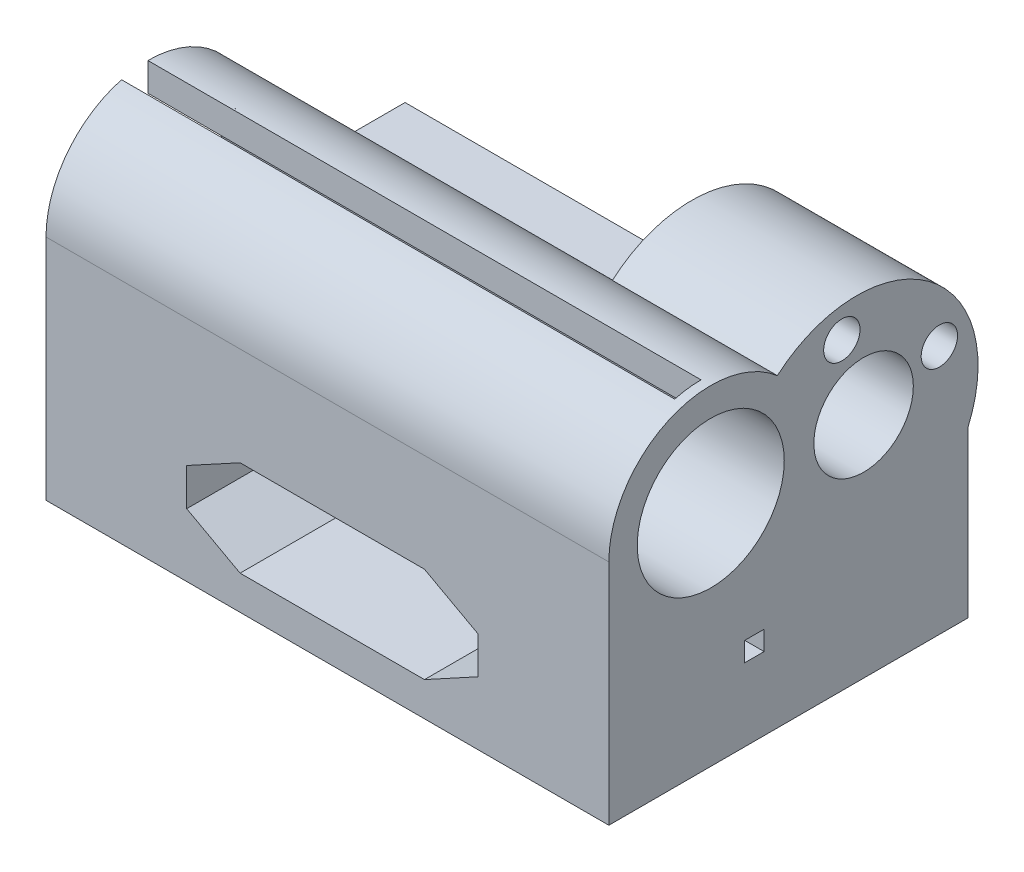
SolidWorks part; units mm, degrees
ref_plane "Front Plane" through (0, 0, 0) normal (0, 0, 1) x (1, 0, 0)
ref_plane "Top Plane" through (0, 0, 0) normal (0, 1, 0) x (1, 0, 0)
ref_plane "Right Plane" through (0, 0, 0) normal (1, 0, 0) x (0, 0, -1)
sketch "Sketch2" plane through (0, 0, 0) normal (0, 1, 0) x (1, 0, 0)
  line L1 (-29, -18.5) -> (29, -18.5)
  line L2 (-29, -18.5) -> (-29, 18.5)
  line L3 (-29, 18.5) -> (29, 18.5)
  line L4 (29, -18.5) -> (29, 18.5)
  line L5 (-29, -18.5) -> (29, 18.5) construction
  line L6 (-29, 18.5) -> (29, -18.5) construction
  point P0 (0, 0)
  dimension "D1" = 58
  dimension "D2" = 37
extrude "Boss-Extrude1" add sketch "Sketch2" along normal blind 17
sketch "Sketch3" plane through (29, 0, 0) normal (1, 0, 0) x (0, 0, -1)
  line L0 (-18.5, 0) -> (18.5, 0) construction
  line L1 (-18.5, 23.5) -> (-18.5, 17)
  line L2 (-18.5, 17) -> (-18.5, 0) construction
  line L5 (2.5, 23.5) -> (2.5, 17)
  line L6 (-18.5, 17) -> (18.5, 17) construction
  line L7 (-18.5, 17) -> (2.5, 17)
  arc A0 (2.5, 23.5) -> (-18.5, 23.5) centre (-8, 23.5) ccw
  dimension "D2" = 21
  dimension "D4" = 23.5
  dimension "D5" = 10.5
extrude "Boss-Extrude2" add sketch "Sketch3" against normal up to surface (58 mm away) up to face at (-29, 8.5, 0)
sketch "Sketch4" plane through (29, 0, 0) normal (1, 0, 0) x (0, 0, -1)
  line L1 (-18.5, 0) -> (18.5, 0) construction
  circle A0 centre (7.0436, 22) radius 12.5
  dimension "D1" = 25
  dimension "D2" = 22
extrude "Boss-Extrude3" add sketch "Sketch4" against normal blind 17
sketch "Sketch5" plane through (0, 0, -18.5) normal (0, 0, -1) x (-1, 0, 0)
  line L0 (-15.5, 6.5) -> (-15.5, 10.35)
  line L1 (-15.5, 10.35) -> (-10, 13.35)
  line L2 (-10, 13.35) -> (9, 13.35)
  line L3 (9, 13.35) -> (14.5, 10.357)
  line L4 (14.5, 10.357) -> (14.5, 6.5)
  line L5 (14.5, 6.5) -> (9, 3.5)
  line L6 (9, 3.5) -> (-10, 3.5)
  line L7 (-10, 3.5) -> (-15.5, 6.5)
  line L8 (-29, 0) -> (29, 0) construction
  line L9 (-29, 17) -> (-29, 0) construction
  line L10 (-23, 5.2045) -> (-23, 14.6536) construction
  line L11 (22, 4.2644) -> (22, 14.6536) construction
  line L12 (-23, 14.6536) -> (22, 14.6536) construction
  line L13 (-0.5, 14.6536) -> (-0.5, 7.909) construction
  line L14 (-29, 8.5) -> (29, 8.5) construction
  line L15 (29, 17) -> (29, 0) construction
  dimension "D1" = 3.85
  dimension "D2" = 3.857
  dimension "D3" = 3
  dimension "D4" = 3
  dimension "D5" = 5.5
  dimension "D6" = 5.5
  dimension "D8" = 5.5
  dimension "D9" = 19
  dimension "D10" = 3.5
  dimension "D11" = 15
  dimension "D12" = 6
  dimension "D13" = 45
extrude "Cut-Extrude1" cut sketch "Sketch5" against normal through all
sketch "Sketch6" plane through (0, 0, -18.5) normal (0, 0, -1) x (-1, 0, 0)
  line L0 (-29, 0) -> (29, 0) construction
  line L1 (-29, 17) -> (-29, 0) construction
  circle A0 centre (-23, 8.5) radius 4.076
  circle A1 centre (22, 8.5) radius 4.076
  dimension "D5" = 8.152
  dimension "D6" = 8.152
  dimension "D1" = 8.5
  dimension "D2" = 8.5
  dimension "D3" = 6
  dimension "D4" = 45
extrude "Cut-Extrude2" cut sketch "Sketch6" against normal blind 23
sketch "Sketch7" plane through (29, 0, 0) normal (1, 0, 0) x (0, 0, -1)
  line L0 (-18.5, 23.5) -> (-18.5, 0) construction
  line L1 (-18.5, 0) -> (18.5, 0) construction
  circle A0 centre (-8, 23.5) radius 7.575
  circle A1 centre (7.7501, 23.5) radius 5.125
  dimension "D1" = 10.25
  dimension "D2" = 15.15
  dimension "D3" = 26.2501
  dimension "D4" = 23.5
extrude "Cut-Extrude3" cut sketch "Sketch7" against normal through all
sketch "Sketch8" plane through (29, 0, 0) normal (1, 0, 0) x (0, 0, -1)
  line L0 (7.7501, 23.5) -> (5.5097, 31.31) construction
  line L3 (7.7501, 23.5) -> (15.5601, 25.7405) construction
  line L4 (5.5097, 31.31) -> (6.0267, 29.5077) construction
  line L7 (15.5601, 25.7405) -> (13.7578, 25.2235) construction
  circle A1 centre (5.5097, 31.31) radius 1.875
  circle A2 centre (15.5601, 25.7405) radius 1.875
  dimension "D1" = 3.75
  dimension "D2" = 6.25
  dimension "D3" = 3.75
  dimension "D7" = 6.25
extrude "Cut-Extrude4" cut sketch "Sketch8" against normal through all
sketch "Sketch12" plane through (-29, 0, 0) normal (-1, 0, 0) x (0, 0, 1)
  line L0 (-18.5, 17) -> (-18.5, 0) construction
  line L1 (4.5, 7.5) -> (2.5, 7.5)
  line L2 (4.5, 7.5) -> (4.5, 9.5)
  line L3 (4.5, 9.5) -> (2.5, 9.5)
  line L4 (2.5, 7.5) -> (2.5, 9.5)
  line L5 (-18.5, 0) -> (18.5, 0) construction
  dimension "D1" = 23
  dimension "D2" = 2
  dimension "D3" = 2
  dimension "D4" = 7.5
extrude "Cut-Extrude6" cut sketch "Sketch12" against normal blind 8
mirror "Mirror1" about plane through (0, 0, 0) normal (1, 0, 0) of "Cut-Extrude6"
sketch "Sketch13" plane through (-29, 0, 0) normal (-1, 0, 0) x (0, 0, 1)
  line L0 (8, 23.5) -> (10.7176, 33.6422) construction
  line L1 (8, 23.5) -> (-2.5, 23.5) construction
  line L2 (8, 23.5) -> (8, 34) construction
  line L3 (9.9606, 30.8169) -> (10.7176, 33.6422)
  line L4 (8, 34) -> (8, 31.075)
  arc A0 (9.9606, 30.8169) -> (8, 31.075) centre (8, 23.5) ccw
  arc A1 (-2.5, 23.5) -> (8, 34) centre (8, 23.5) ccw
  arc A2 (18.5, 23.5) -> (-2.5, 23.5) centre (8, 23.5) ccw construction
  arc A3 (1.1397, 31.449) -> (-2.5, 23.5) centre (8, 23.5) ccw construction
  circle A4 centre (8, 23.5) radius 7.575 construction
  circle M5 centre (8, 23.5) radius 7.575
  arc M8 (18.5, 23.5) -> (-2.5, 23.5) centre (8, 23.5) ccw
  dimension "D1" = 15
  dimension "D2" = 90
extrude "Cut-Extrude7" cut sketch "Sketch13" against normal blind 57 contours L4 L3 M8 M5 region at (-29, 32.5126, 9.1865)
sketch "Sketch14" plane through (0, 0, 0) normal (0, -1, 0) x (1, 0, 0)
  line L0 (0.5, -11.5) -> (29, -11.5) construction
  line L1 (29, 18.5) -> (29, -18.5) construction
  line L2 (0.5, -11.5) -> (0.5, -18.5) construction
  line L3 (29, -18.5) -> (-29, -18.5) construction
  circle A0 centre (0.5, -11.5) radius 1.5
  dimension "D1" = 3
  dimension "D2" = 7
  dimension "D3" = 28.5
extrude "Cut-Extrude8" cut sketch "Sketch14" against normal through all
